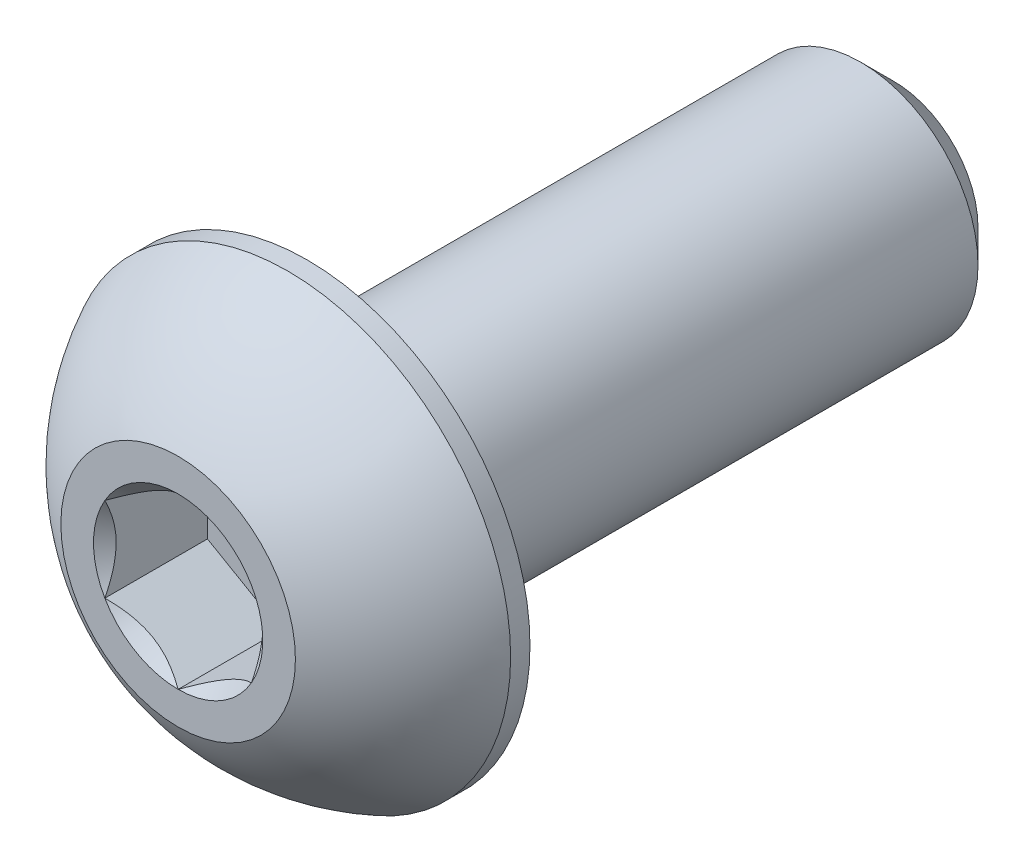
SolidWorks part; units mm, degrees
material "Alloy Steel"
ref_plane "Front Plane" through (0, 0, 0) normal (0, 0, 1) x (1, 0, 0)
ref_plane "Top Plane" through (0, 0, 0) normal (0, 1, 0) x (1, 0, 0)
ref_plane "Right Plane" through (0, 0, 0) normal (1, 0, 0) x (0, 0, -1)
sketch "Sketch1" plane through (0, 0, 0) normal (1, 0, 0) x (0, 0, -1)
  line L0 (-6.1, 0) -> (6.1, 0) construction
  line L1 (-3.9, 3.8) -> (-3.9, -3.8) construction
  line L2 (6.1, 2) -> (6.1, -2) construction
  line L3 (6.0563, 2.0758) -> (6.4063, 1.4696) construction
  line L4 (6.4063, 1.4696) -> (6.7563, 2.0758) construction
  line L5 (6.7563, 2.0758) -> (6.0563, 2.0758) construction
  line L6 (6.1, 2) -> (6.7125, 2) construction
  line L7 (6.4063, 2.0758) -> (6.4063, 2) construction
  line L8 (6.4063, 2) -> (6.4063, 1.5453) construction
  line L9 (6.4063, 1.5453) -> (6.4063, 1.4696) construction
  line L10 (6.3625, 1.5453) -> (6.45, 1.5453)
  line L11 (6.0781, 2.0379) -> (6.7344, 2.0379)
  line L12 (6.45, 1.5453) -> (6.7344, 2.0379)
  line L13 (6.3625, 1.5453) -> (6.0781, 2.0379)
  line L14 (-6.1, 1.25) -> (-6.1, -1.25) construction
  line L15 (6.1, 2) -> (-3.9, 2) construction
  point P3 (-3.9, 0)
  point P6 (-4.35, 0)
  point P21 (6.4063, 2.0379)
  point P24 (-4.23, 3.8)
  point P25 (4.35, -2)
  point P26 (-6.1, 2)
  dimension "Head Height" = 2.2
  dimension "Length" = 10
  dimension "Head Dia" = 7.6
  dimension "Thread Dia" = 4
  dimension "Pitch" = 0.7
  dimension "D2" = 0.0875
  dimension "Drive Size" = 2.5
  dimension "D1" = 1.75
  dimension "D3" = 0.33
  dimension "D4" = 1.75
sketch "Sketch2" plane through (0, 0, 0) normal (1, 0, 0) x (0, 0, -1)
  line L0 (-6.1, 0) -> (6.1, 0)
  line L1 (6.1, 0) -> (6.1, 1.44)
  line L2 (6.1, 2) -> (6.1, -2) construction
  line L3 (6.1, 1.44) -> (5.54, 2)
  line L4 (5.54, 2) -> (-3.9, 2)
  line L5 (-3.9, 3.8) -> (-3.9, -3.8) construction
  line L6 (-3.9, 2) -> (-3.9, 3.8)
  line L7 (-3.9, 3.8) -> (-4.23, 3.8)
  line L8 (6.1, 2) -> (6.7125, 2) construction
  line L9 (-6.1, 0) -> (-6.1, 2)
  arc A0 (-6.1, 2) -> (-4.23, 3.8) centre (-2.3736, 0) cw
  dimension "D1" = 0.56
  dimension "D2" = 45
revolve "Revolve1" add sketch "Sketch2" angle 360 about L0
sketch "Sketch3" plane through (0, 0, 6.1) normal (0, 0, 1) x (1, 0, 0)
  line L1 (0, 1.4434) -> (-1.25, 0.7217)
  line L2 (-1.25, 0.7217) -> (-1.25, -0.7217)
  line L3 (-1.25, -0.7217) -> (0, -1.4434)
  line L4 (0, -1.4434) -> (1.25, -0.7217)
  line L5 (1.25, -0.7217) -> (1.25, 0.7217)
  line L6 (1.25, 0.7217) -> (0, 1.4434)
  circle A0 centre (0, 0) radius 1.25 construction
  dimension "D1" = 2.5
extrude "Cut-Extrude1" cut sketch "Sketch3" against normal up to vertex (1.75 mm away) up to point (0, 0, 4.35)
sketch "Sketch4" plane through (0, 0, 6.1) normal (0, 0, 1) x (1, 0, 0)
  circle A0 centre (0, 0) radius 1.4434
extrude "Cut-Extrude2" cut sketch "Sketch4" against normal blind 10 draft 45
split "Split1" [suppressed] bodies to split 106
sketch "Sketch5" [suppressed] plane through (0, 0, -6.1) normal (0, 0, -1) x (-1, 0, 0)
  circle A0 centre (0, 0) radius 2 construction
  circle A1 centre (0, 0) radius 2
curve "Helix/Spiral1" [suppressed] pitch 0.7 height 10.7 turns 15.2857
sketch "Sketch6" [suppressed] plane through (0, 0, 0) normal (1, 0, 0) x (0, 0, -1)
  line L0 (6.3625, 1.5453) -> (6.45, 1.5453) construction
  line L1 (6.3625, 1.5453) -> (6.0781, 2.0379) construction
  line L2 (6.0781, 2.0379) -> (6.7344, 2.0379) construction
  line L3 (6.45, 1.5453) -> (6.7344, 2.0379) construction
  line L4 (6.3625, 1.5453) -> (6.45, 1.5453)
  line L5 (6.3625, 1.5453) -> (6.0781, 2.0379)
  line L6 (6.0781, 2.0379) -> (6.7344, 2.0379)
  line L7 (6.45, 1.5453) -> (6.7344, 2.0379)
sweep "Cut-Sweep1" [suppressed] cut profiles "Sketch6" path "Helix/Spiral1"
sketch "Sketch7" [suppressed] plane through (0, 0, 3.9) normal (0, 0, -1) x (-1, 0, 0)
  circle A1 centre (0, 0) radius 2
  circle A2 centre (0, 0) radius 2
  dimension "D1" = 0
extrude "Boss-Extrude1" [suppressed] add sketch "Sketch7" along normal blind 10 draft 30
equation "\"D2@Sketch1\" = \"Pitch@Sketch1\" / 8"
equation "\"D1@Sketch1\"=\"Drive Size@Sketch1\"*.7"
equation "\"D3@Sketch1\"=\"Head Height@Sketch1\"*.15"
equation "\"D1@Sketch2\"=\"Pitch@Sketch1\"*.8"
equation "\"D1@Sketch3\"=\"Drive Size@Sketch1\""
equation "\"D4@Helix/Spiral1\"=\"Pitch@Sketch1\""
equation "\"D3@Helix/Spiral1\"=\"Length@Sketch1\"+\"Pitch@Sketch1\""
equation "\"D4@Sketch1\"=\"Pitch@Sketch1\"*2.5"
